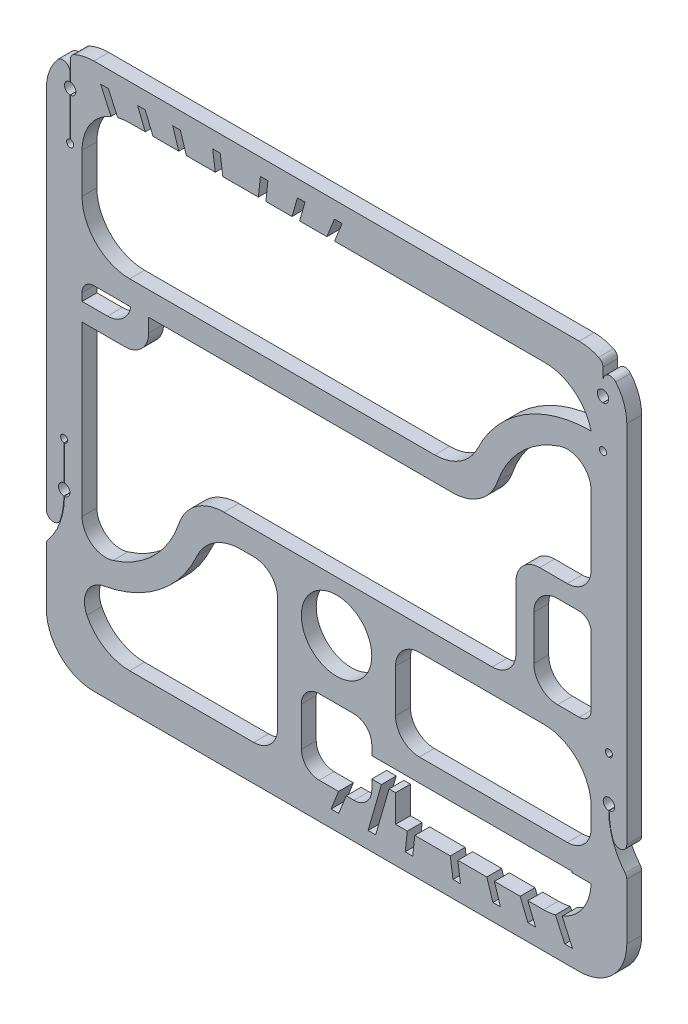
SolidWorks part; units mm, degrees
ref_plane "Front Plane" through (0, 0, 0) normal (0, 0, 1) x (1, 0, 0)
ref_plane "Top Plane" through (0, 0, 0) normal (0, 1, 0) x (1, 0, 0)
ref_plane "Right Plane" through (0, 0, 0) normal (1, 0, 0) x (0, 0, -1)
sketch "Sketch1" plane through (0, 0, 0) normal (0, 0, 1) x (1, 0, 0)
  line L0 (44.642, 21.8842) -> (44.642, 18.0742) construction
  line L1 (-10.1934, 21.8842) -> (51.7832, 21.8842)
  line L2 (-10.1934, 21.8842) -> (-10.1934, -36.406)
  line L3 (-10.1934, -36.406) -> (51.7832, -36.406)
  line L4 (51.7832, 21.8842) -> (51.7832, -36.406)
  line L5 (47.9732, -32.596) -> (-6.3834, -32.596)
  line L6 (47.9732, -32.596) -> (47.9732, 18.0742)
  line L7 (47.9732, 18.0742) -> (-6.3834, 18.0742)
  line L8 (-6.3834, -32.596) -> (-6.3834, 18.0742)
  line L9 (44.642, 19.9792) -> (-35.1587, 19.9792) construction
  line L10 (-6.3834, -31.0517) -> (-10.1934, -31.0517) construction
  line L11 (-8.2884, -31.0517) -> (-8.2884, 6.9585) construction
  line L12 (20.6521, 19.9792) -> (21.1982, 19.9792) construction
  line L14 (3.0779, -32.596) -> (3.0779, -36.406) construction
  line L15 (3.0779, -34.501) -> (37.3423, -34.501) construction
  line L16 (47.9732, -11.3911) -> (47.9732, 12.9942) construction
  line L17 (51.7832, 15.2205) -> (47.9732, 15.2205) construction
  line L18 (49.8782, 15.2205) -> (49.8782, -0.9437) construction
  line L20 (20.9378, -34.501) -> (20.3916, -34.501) construction
  line L21 (-6.3834, 8.0412) -> (-6.3834, -11.3911) construction
  dimension "D1" = 3.81
  dimension "D2" = 3.81
extrude "Boss-Extrude1" add sketch "Sketch1" along normal blind 1.5875
sketch "Sketch2" plane through (0, 0, 0) normal (0, 0, -1) x (-1, 0, 0)
  line L0 (-47.9732, -32.596) -> (-47.9732, 18.0742) construction
  line L1 (-34.8696, 3.653) -> (6.3834, 3.653)
  line L2 (-47.9732, 3.653) -> (-47.9732, 0.8076)
  line L3 (-37.4096, 1.113) -> (6.3834, 1.113)
  line L4 (6.3834, 3.653) -> (6.3834, 1.113)
  line L5 (6.3834, 18.0742) -> (6.3834, -32.596) construction
  line L6 (-33.4496, 1.113) -> (-36.4496, 1.113) construction
  line L7 (1.2504, -12.887) -> (-36.4496, -12.887) construction
  line L8 (-47.9732, -15.427) -> (-6.8239, -15.427)
  line L9 (-47.9732, -15.427) -> (-47.9732, -12.887)
  line L10 (-47.9732, -12.887) -> (-4.5259, -12.887)
  line L11 (1.357, -21.2563) -> (14.2432, -21.2563) construction
  line L12 (6.3834, -23.7963) -> (6.3834, -26.3363)
  line L13 (-47.9732, 14.2166) -> (-47.9732, 11.6766)
  arc A0 (-47.9732, 11.6766) -> (-37.4096, 1.113) centre (-47.9732, 1.113) cw
  arc A1 (-47.9732, 14.2166) -> (-34.8696, 3.653) centre (-47.9732, 0.8076) cw
  arc A2 (6.3834, -23.7963) -> (-4.5259, -12.887) centre (6.3834, -12.887) cw
  arc A3 (-6.8239, -15.427) -> (6.3834, -26.3363) centre (6.3834, -12.887) ccw
  circle A5 centre (1.357, -18.2591) radius 2.9972 construction
  line M5 (-47.9732, -32.596) -> (-47.9732, 18.0742)
  line M7 (6.3834, 18.0742) -> (6.3834, -32.596)
  dimension "D5" = 2.54
  dimension "D1" = 2.54
  dimension "D2" = 2.54
  dimension "D3" = 2.54
  dimension "D4" = 2.54
  dimension "D6" = 2.54
  dimension "D7" = 2.54
extrude "Boss-Extrude2" add sketch "Sketch2" against normal up to surface (1.5875 mm away) contours A1 A0 L3 L1 M5 M7 | L10 L8 M5 M7 region at (14.2431, 3.0939, 0) region at (-5.8234, -25.0663, 0) up to face at (20.7949, -7.2609, 1.5875)
sketch "Sketch3" plane through (0, 0, 0) normal (0, 0, -1) x (-1, 0, 0)
  line L0 (-47.9732, -1.1649) -> (-39.9496, -1.1649)
  line L1 (-47.9732, -12.887) -> (-47.9732, 11.6766) construction
  line L2 (-39.9496, -4.387) -> (-39.9496, -11.387) construction
  line L3 (-39.9496, -1.1649) -> (-39.9496, -12.887)
  line L4 (-47.9732, -12.887) -> (-4.5259, -12.887) construction
  line L5 (-39.9496, -12.887) -> (-41.8546, -12.887)
  line L6 (-41.8546, -12.887) -> (-41.8546, -3.0699)
  line L7 (-41.8546, -3.0699) -> (-47.9732, -3.0699)
  line L8 (-47.9732, -3.0699) -> (-47.9732, -1.1649)
  line L9 (-42.9468, 0.7401) -> (-53.4831, 0.7401) construction
  line L10 (-0.7296, 1.113) -> (-0.7296, -2.887)
  line L11 (-37.4096, 1.113) -> (6.3834, 1.113) construction
  line L12 (-1.9996, -2.887) -> (1.2504, -2.887) construction
  line L13 (-0.7296, -2.887) -> (6.3834, -2.887)
  line L14 (6.3834, 1.113) -> (6.3834, -23.7963) construction
  line L15 (6.3834, -2.887) -> (6.3834, -0.982)
  line L16 (6.3834, -0.982) -> (1.1754, -0.982)
  line L17 (1.1754, -0.982) -> (1.1754, 1.113)
  line L18 (1.1754, 1.113) -> (-0.7296, 1.113)
  circle A0 centre (-42.9468, 3.7373) radius 2.9972 construction
  dimension "D1" = 1.905
  dimension "D2" = 1.905
  dimension "D3" = 1.905
  dimension "D4" = 1.905
  dimension "D5" = 1.27
  dimension "D6" = 1.905
extrude "Boss-Extrude3" add sketch "Sketch3" against normal up to surface (1.5875 mm away) up to face at (20.8645, -5.9566, 1.5875)
fillet "Fillet1" radius 5.08 4 edges at (51.7832, -36.406, 0.7937) (-10.1934, -36.406, 0.7937) (-10.1934, 21.8842, 0.7937) (51.7832, 21.8842, 0.7937)
fillet "Fillet2" radius 5.08 10 edges at (6.8239, -15.427, 0.7937) (47.9732, -15.427, 0.7937) (47.9732, -32.596, 0.7937) (-6.3834, -32.596, 0.7937) (34.8696, 3.653, 0.7938) (-6.3834, 3.653, 0.7937) (47.9732, 18.0742, 0.7937) (-6.3834, 18.0742, 0.7937) (4.5259, -12.887, 0.7937) (37.4096, 1.113, 0.7938)
fillet "Fillet3" radius 2.54 10 edges at (41.8546, -3.0699, 0.7938) (39.9496, -12.887, 0.7938) (41.8546, -12.887, 0.7938) (39.9496, -1.1649, 0.7938) (47.9732, -1.1649, 0.7938) (-1.1754, -0.982, 0.7938) (0.7296, -2.887, 0.7938) (47.9732, 11.6766, 0.7937) (-6.3834, -26.3363, 0.7937) (-6.3834, -23.7963, 0.7937)
fillet "Fillet4" radius 1.27 3 edges at (47.9732, -12.887, 0.7937) (47.9732, -3.0699, 0.7938) (-6.3834, 1.113, 0.7938)
sketch "Sketch5" plane through (0, 0, 0) normal (0, 0, -1) x (-1, 0, 0)
  line L0 (-42.8932, -15.427) -> (-10.5066, -15.427) construction
  line L1 (-27.0941, -15.427) -> (-14.4957, -15.427)
  line L2 (-27.0941, -15.427) -> (-27.0941, -32.596)
  line L3 (-27.0941, -32.596) -> (-14.4957, -32.596)
  line L4 (-14.4957, -15.427) -> (-14.4957, -32.596)
  line L5 (1.3034, -32.596) -> (-42.8932, -32.596) construction
  line L6 (-24.5541, -18.2972) -> (-27.0941, -18.2972) construction
  line L9 (-17.0357, -18.2972) -> (-14.4957, -18.2972) construction
  circle A1 centre (-20.7949, -18.2972) radius 3.7592 construction
  dimension "D1" = 2.54
extrude "Boss-Extrude4" add sketch "Sketch5" against normal up to surface (1.5875 mm away) up to face at (-4.5227, -0.0173, 1.5875)
sketch "Sketch6" plane through (0, 0, 0) normal (0, 0, -1) x (-1, 0, 0)
  circle A0 centre (-20.7949, -18.2972) radius 3.7592 construction
  circle A1 centre (-20.7949, -18.2972) radius 3.7592
extrude "Cut-Extrude2" cut sketch "Sketch6" against normal up to surface (1.5875 mm away) up to face at (4.768, -24.4396, 1.5875)
sketch "Sketch7" plane through (0, 0, 0) normal (0, 0, -1) x (-1, 0, 0)
  line L0 (-27.0941, -15.427) -> (-27.0941, -32.596) construction
  line L1 (-24.5541, -24.5964) -> (-17.0357, -24.5964)
  line L2 (-24.5541, -24.5964) -> (-24.5541, -32.596)
  line L3 (-24.5541, -32.596) -> (-17.0357, -32.596)
  line L4 (-17.0357, -24.5964) -> (-17.0357, -32.596)
  line L5 (-14.4957, -32.596) -> (-14.4957, -15.427) construction
  line L6 (1.3034, -32.596) -> (-14.4957, -32.596) construction
  line L7 (-20.7949, -22.0564) -> (-6.5424, -22.0564) construction
  line L8 (-20.7949, -22.0564) -> (-20.7949, -21.3452) construction
  circle A0 centre (-20.7949, -18.2972) radius 3.7592 construction
  dimension "D1" = 2.54
  dimension "D2" = 2.54
  dimension "D3" = 2.54
extrude "Cut-Extrude3" cut sketch "Sketch7" against normal up to surface (1.5875 mm away) up to face at (24.5541, -18.2972, 1.5875)
fillet "Fillet5" radius 1.905 4 edges at (24.5541, -32.596, 0.7937) (17.0357, -32.596, 0.7938) (17.0357, -24.5964, 0.7938) (24.5541, -24.5964, 0.7938)
sketch "Sketch8" plane through (0, 0, 0) normal (0, 0, -1) x (-1, 0, 0)
  line L0 (-47.9732, -27.516) -> (-47.9732, -20.507) construction
  line L1 (-47.9732, -25.103) -> (-27.0941, -25.103)
  line L2 (-47.9732, -25.103) -> (-47.9732, -27.643)
  line L3 (-47.9732, -27.643) -> (-27.0941, -27.643)
  line L4 (-27.0941, -25.103) -> (-27.0941, -27.643)
  line L5 (-27.0941, -15.427) -> (-27.0941, -32.596) construction
  line L6 (-45.7916, -27.643) -> (-20.3916, -27.643) construction
  dimension "D1" = 2.54
extrude "Boss-Extrude5" add sketch "Sketch8" against normal up to surface (1.5875 mm away) up to face at (20.7949, -28.5962, 1.5875)
fillet "Fillet6" radius 2.54 5 edges at (27.0941, -15.427, 0.7937) (14.4957, -15.427, 0.7937) (14.4957, -32.596, 0.7937) (27.0941, -25.103, 0.7937) (47.9732, -25.103, 0.7937)
sketch "Sketch4" plane through (0, 0, 0) normal (0, 0, -1) x (-1, 0, 0)
  line L0 (3.2504, -2.887) -> (4.7504, -4.387) construction
  line L1 (4.7504, -11.387) -> (3.2504, -12.887) construction
  line L2 (3.2504, -2.887) -> (4.7504, -4.387)
  line L3 (4.7504, -11.387) -> (3.2504, -12.887)
  line L4 (4.7504, -4.387) -> (4.7504, -11.387) construction
  line L5 (4.7504, -4.387) -> (4.7504, -11.387)
  line L6 (3.2504, -2.887) -> (3.2504, -12.887)
  line L32 (4.2018, 13.1212) -> (4.2018, 15.0262)
  line L33 (4.2018, 15.0262) -> (1.9539, 15.0262)
  line L34 (1.9539, 15.0262) -> (4.2018, 19.9792)
  line L35 (4.2018, 19.9792) -> (3.6556, 19.9792)
  line L36 (3.6556, 19.9792) -> (1.4078, 15.0262)
  line L37 (1.4078, 15.0262) -> (-1.7417, 15.0262)
  line L38 (-1.7417, 15.0262) -> (0.2648, 19.9792)
  line L39 (0.2648, 19.9792) -> (-0.2814, 19.9792)
  line L40 (-0.2814, 19.9792) -> (-2.2879, 15.0262)
  line L41 (-2.2879, 15.0262) -> (-5.0437, 15.0262)
  line L42 (-5.0437, 15.0262) -> (-3.469, 19.9792)
  line L43 (-3.469, 19.9792) -> (-4.0152, 19.9792)
  line L44 (-4.0152, 19.9792) -> (-5.5899, 15.0262)
  line L45 (-5.5899, 15.0262) -> (-8.3965, 15.0262)
  line L46 (-8.3965, 15.0262) -> (-7.7108, 19.9792)
  line L47 (-7.7108, 19.9792) -> (-8.257, 19.9792)
  line L48 (-8.257, 19.9792) -> (-8.9427, 15.0262)
  line L49 (-8.9427, 15.0262) -> (-12.2319, 15.0262)
  line L50 (-12.2319, 15.0262) -> (-12.7781, 19.9792)
  line L51 (-12.7781, 19.9792) -> (-13.3242, 19.9792)
  line L52 (-13.3242, 19.9792) -> (-12.7781, 15.0262)
  line L53 (-12.7781, 15.0262) -> (-15.2926, 15.0262)
  line L54 (-15.2926, 15.0262) -> (-16.7151, 19.9792)
  line L55 (-16.7151, 19.9792) -> (-17.2612, 19.9792)
  line L56 (-17.2612, 19.9792) -> (-15.8388, 15.0262)
  line L57 (-15.8388, 15.0262) -> (-18.6963, 15.0262)
  line L58 (-18.6963, 15.0262) -> (-20.6521, 19.9792)
  line L59 (-20.6521, 19.9792) -> (-21.1982, 19.9792)
  line L60 (-21.1982, 19.9792) -> (-19.2425, 15.0262)
  line L61 (-19.2425, 15.0262) -> (-21.1982, 15.0262)
  line L62 (-21.1982, 15.0262) -> (-21.1982, 13.1212)
  line L63 (-21.1982, 13.1212) -> (4.2018, 13.1212)
  line L64 (4.2018, 13.1212) -> (4.2018, 15.0262) construction
  line L65 (4.2018, 15.0262) -> (1.9539, 15.0262) construction
  line L66 (1.9539, 15.0262) -> (4.2018, 19.9792) construction
  line L67 (4.2018, 19.9792) -> (3.6556, 19.9792) construction
  line L68 (3.6556, 19.9792) -> (1.4078, 15.0262) construction
  line L69 (1.4078, 15.0262) -> (-1.7417, 15.0262) construction
  line L70 (-1.7417, 15.0262) -> (0.2648, 19.9792) construction
  line L71 (0.2648, 19.9792) -> (-0.2814, 19.9792) construction
  line L72 (-0.2814, 19.9792) -> (-2.2879, 15.0262) construction
  line L73 (-2.2879, 15.0262) -> (-5.0437, 15.0262) construction
  line L74 (-5.0437, 15.0262) -> (-3.469, 19.9792) construction
  line L75 (-3.469, 19.9792) -> (-4.0152, 19.9792) construction
  line L76 (-4.0152, 19.9792) -> (-5.5899, 15.0262) construction
  line L77 (-5.5899, 15.0262) -> (-8.3965, 15.0262) construction
  line L78 (-8.3965, 15.0262) -> (-7.7108, 19.9792) construction
  line L79 (-7.7108, 19.9792) -> (-8.257, 19.9792) construction
  line L80 (-8.257, 19.9792) -> (-8.9427, 15.0262) construction
  line L81 (-8.9427, 15.0262) -> (-12.2319, 15.0262) construction
  line L82 (-12.2319, 15.0262) -> (-12.7781, 19.9792) construction
  line L83 (-12.7781, 19.9792) -> (-13.3242, 19.9792) construction
  line L84 (-13.3242, 19.9792) -> (-12.7781, 15.0262) construction
  line L85 (-12.7781, 15.0262) -> (-15.2926, 15.0262) construction
  line L86 (-15.2926, 15.0262) -> (-16.7151, 19.9792) construction
  line L87 (-16.7151, 19.9792) -> (-17.2612, 19.9792) construction
  line L88 (-17.2612, 19.9792) -> (-15.8388, 15.0262) construction
  line L89 (-15.8388, 15.0262) -> (-18.6963, 15.0262) construction
  line L90 (-18.6963, 15.0262) -> (-20.6521, 19.9792) construction
  line L91 (-20.6521, 19.9792) -> (-21.1982, 19.9792) construction
  line L92 (-21.1982, 19.9792) -> (-19.2425, 15.0262) construction
  line L93 (-19.2425, 15.0262) -> (-21.1982, 15.0262) construction
  line L94 (-21.1982, 15.0262) -> (-21.1982, 13.1212) construction
  line L95 (-21.1982, 13.1212) -> (4.2018, 13.1212) construction
  line L96 (-45.7916, -27.643) -> (-45.7916, -29.548)
  line L97 (-45.7916, -29.548) -> (-43.5438, -29.548)
  line L98 (-43.5438, -29.548) -> (-45.7916, -34.501)
  line L99 (-45.7916, -34.501) -> (-45.2455, -34.501)
  line L100 (-45.2455, -34.501) -> (-42.9976, -29.548)
  line L101 (-42.9976, -29.548) -> (-39.8482, -29.548)
  line L102 (-39.8482, -29.548) -> (-41.8546, -34.501)
  line L103 (-41.8546, -34.501) -> (-41.3085, -34.501)
  line L104 (-41.3085, -34.501) -> (-39.302, -29.548)
  line L105 (-39.302, -29.548) -> (-36.5462, -29.548)
  line L106 (-36.5462, -29.548) -> (-38.1208, -34.501)
  line L107 (-38.1208, -34.501) -> (-37.5747, -34.501)
  line L108 (-37.5747, -34.501) -> (-36, -29.548)
  line L109 (-36, -29.548) -> (-33.1934, -29.548)
  line L110 (-33.1934, -29.548) -> (-33.879, -34.501)
  line L111 (-33.879, -34.501) -> (-33.3329, -34.501)
  line L112 (-33.3329, -34.501) -> (-32.6472, -29.548)
  line L113 (-32.6472, -29.548) -> (-29.358, -29.548)
  line L114 (-29.358, -29.548) -> (-28.8118, -34.501)
  line L115 (-28.8118, -34.501) -> (-28.2656, -34.501)
  line L116 (-28.2656, -34.501) -> (-28.8118, -29.548)
  line L117 (-28.8118, -29.548) -> (-26.2973, -29.548)
  line L118 (-26.2973, -29.548) -> (-24.8748, -34.501)
  line L119 (-24.8748, -34.501) -> (-24.3286, -34.501)
  line L120 (-24.3286, -34.501) -> (-25.7511, -29.548)
  line L121 (-25.7511, -29.548) -> (-22.8935, -29.548)
  line L122 (-22.8935, -29.548) -> (-20.9378, -34.501)
  line L123 (-20.9378, -34.501) -> (-20.3916, -34.501)
  line L124 (-20.3916, -34.501) -> (-22.3474, -29.548)
  line L125 (-22.3474, -29.548) -> (-20.3916, -29.548)
  line L126 (-20.3916, -29.548) -> (-20.3916, -27.643)
  line L127 (-20.3916, -27.643) -> (-45.7916, -27.643)
  line L128 (-45.7916, -27.643) -> (-45.7916, -29.548) construction
  line L129 (-45.7916, -29.548) -> (-43.5438, -29.548) construction
  line L130 (-43.5438, -29.548) -> (-45.7916, -34.501) construction
  line L131 (-45.7916, -34.501) -> (-45.2455, -34.501) construction
  line L132 (-45.2455, -34.501) -> (-42.9976, -29.548) construction
  line L133 (-42.9976, -29.548) -> (-39.8482, -29.548) construction
  line L134 (-39.8482, -29.548) -> (-41.8546, -34.501) construction
  line L135 (-41.8546, -34.501) -> (-41.3085, -34.501) construction
  line L136 (-41.3085, -34.501) -> (-39.302, -29.548) construction
  line L137 (-39.302, -29.548) -> (-36.5462, -29.548) construction
  line L138 (-36.5462, -29.548) -> (-38.1208, -34.501) construction
  line L139 (-38.1208, -34.501) -> (-37.5747, -34.501) construction
  line L140 (-37.5747, -34.501) -> (-36, -29.548) construction
  line L141 (-36, -29.548) -> (-33.1934, -29.548) construction
  line L142 (-33.1934, -29.548) -> (-33.879, -34.501) construction
  line L143 (-33.879, -34.501) -> (-33.3329, -34.501) construction
  line L144 (-33.3329, -34.501) -> (-32.6472, -29.548) construction
  line L145 (-32.6472, -29.548) -> (-29.358, -29.548) construction
  line L146 (-29.358, -29.548) -> (-28.8118, -34.501) construction
  line L147 (-28.8118, -34.501) -> (-28.2656, -34.501) construction
  line L148 (-28.2656, -34.501) -> (-28.8118, -29.548) construction
  line L149 (-28.8118, -29.548) -> (-26.2973, -29.548) construction
  line L150 (-26.2973, -29.548) -> (-24.8748, -34.501) construction
  line L151 (-24.8748, -34.501) -> (-24.3286, -34.501) construction
  line L152 (-24.3286, -34.501) -> (-25.7511, -29.548) construction
  line L153 (-25.7511, -29.548) -> (-22.8935, -29.548) construction
  line L154 (-22.8935, -29.548) -> (-20.9378, -34.501) construction
  line L155 (-20.9378, -34.501) -> (-20.3916, -34.501) construction
  line L156 (-20.3916, -34.501) -> (-22.3474, -29.548) construction
  line L157 (-22.3474, -29.548) -> (-20.3916, -29.548) construction
  line L158 (-20.3916, -29.548) -> (-20.3916, -27.643) construction
  line L159 (-20.3916, -27.643) -> (-45.7916, -27.643) construction
  line L263 (4.3288, 12.9942) -> (4.3288, 15.1532)
  line L264 (4.3288, 15.1532) -> (2.151, 15.1532)
  line L265 (2.151, 15.1532) -> (4.3989, 20.1062)
  line L266 (4.3989, 20.1062) -> (3.5738, 20.1062)
  line L267 (3.5738, 20.1062) -> (1.3259, 15.1532)
  line L268 (1.3259, 15.1532) -> (-1.5532, 15.1532)
  line L269 (-1.5532, 15.1532) -> (0.4532, 20.1062)
  line L270 (0.4532, 20.1062) -> (-0.367, 20.1062)
  line L271 (-0.367, 20.1062) -> (-2.3735, 15.1532)
  line L272 (-2.3735, 15.1532) -> (-4.8701, 15.1532)
  line L273 (-4.8701, 15.1532) -> (-3.2954, 20.1062)
  line L274 (-3.2954, 20.1062) -> (-4.1081, 20.1062)
  line L275 (-4.1081, 20.1062) -> (-5.6828, 15.1532)
  line L276 (-5.6828, 15.1532) -> (-8.2507, 15.1532)
  line L277 (-8.2507, 15.1532) -> (-7.565, 20.1062)
  line L278 (-7.565, 20.1062) -> (-8.3676, 20.1062)
  line L279 (-8.3676, 20.1062) -> (-9.0533, 15.1532)
  line L280 (-9.0533, 15.1532) -> (-12.1181, 15.1532)
  line L281 (-12.1181, 15.1532) -> (-12.6643, 20.1062)
  line L282 (-12.6643, 20.1062) -> (-13.466, 20.1062)
  line L283 (-13.466, 20.1062) -> (-12.9198, 15.1532)
  line L284 (-12.9198, 15.1532) -> (-15.1969, 15.1532)
  line L285 (-15.1969, 15.1532) -> (-16.6194, 20.1062)
  line L286 (-16.6194, 20.1062) -> (-17.4298, 20.1062)
  line L287 (-17.4298, 20.1062) -> (-16.0074, 15.1532)
  line L288 (-16.0074, 15.1532) -> (-18.6099, 15.1532)
  line L289 (-18.6099, 15.1532) -> (-20.5657, 20.1062)
  line L290 (-20.5657, 20.1062) -> (-21.3849, 20.1062)
  line L291 (-21.3849, 20.1062) -> (-19.4292, 15.1532)
  line L292 (-19.4292, 15.1532) -> (-21.3252, 15.1532)
  line L293 (-21.3252, 15.1532) -> (-21.3252, 12.9942)
  line L294 (-21.3252, 12.9942) -> (4.3288, 12.9942)
  line L295 (-45.9186, -27.516) -> (-45.9186, -29.675)
  line L296 (-45.9186, -29.675) -> (-43.7409, -29.675)
  line L297 (-43.7409, -29.675) -> (-45.9887, -34.628)
  line L298 (-45.9887, -34.628) -> (-45.1636, -34.628)
  line L299 (-45.1636, -34.628) -> (-42.9158, -29.675)
  line L300 (-42.9158, -29.675) -> (-40.0367, -29.675)
  line L301 (-40.0367, -29.675) -> (-42.0431, -34.628)
  line L302 (-42.0431, -34.628) -> (-41.2229, -34.628)
  line L303 (-41.2229, -34.628) -> (-39.2164, -29.675)
  line L304 (-39.2164, -29.675) -> (-36.7198, -29.675)
  line L305 (-36.7198, -29.675) -> (-38.2945, -34.628)
  line L306 (-38.2945, -34.628) -> (-37.4818, -34.628)
  line L307 (-37.4818, -34.628) -> (-35.9071, -29.675)
  line L308 (-35.9071, -29.675) -> (-33.3392, -29.675)
  line L309 (-33.3392, -29.675) -> (-34.0248, -34.628)
  line L310 (-34.0248, -34.628) -> (-33.2222, -34.628)
  line L311 (-33.2222, -34.628) -> (-32.5366, -29.675)
  line L312 (-32.5366, -29.675) -> (-29.4717, -29.675)
  line L313 (-29.4717, -29.675) -> (-28.9256, -34.628)
  line L314 (-28.9256, -34.628) -> (-28.1239, -34.628)
  line L315 (-28.1239, -34.628) -> (-28.67, -29.675)
  line L316 (-28.67, -29.675) -> (-26.3929, -29.675)
  line L317 (-26.3929, -29.675) -> (-24.9705, -34.628)
  line L318 (-24.9705, -34.628) -> (-24.16, -34.628)
  line L319 (-24.16, -34.628) -> (-25.5825, -29.675)
  line L320 (-25.5825, -29.675) -> (-22.9799, -29.675)
  line L321 (-22.9799, -29.675) -> (-21.0242, -34.628)
  line L322 (-21.0242, -34.628) -> (-20.205, -34.628)
  line L323 (-20.205, -34.628) -> (-22.1607, -29.675)
  line L324 (-22.1607, -29.675) -> (-20.2646, -29.675)
  line L325 (-20.2646, -29.675) -> (-20.2646, -27.516)
  line L326 (-20.2646, -27.516) -> (-45.9186, -27.516)
  dimension "D1" = 0
  dimension "D2" = 0
  dimension "D3" = 0.127
  dimension "D4" = 0.127
extrude "Cut-Extrude1" cut sketch "Sketch4" against normal up to surface (1.5875 mm away) up to face at (37.2819, -20.5167, 1.5875)
sketch "Sketch9" plane through (0, 0, 0) normal (0, 0, -1) x (-1, 0, 0)
  circle A0 centre (-49.2432, 18.0742) radius 0.6096 construction
  circle A1 centre (7.6534, 18.0742) radius 0.6096 construction
  circle A2 centre (8.2884, -19.3286) radius 0.6096 construction
  circle A3 centre (-49.8782, -19.3286) radius 0.6096 construction
  circle A4 centre (-49.2432, 18.0742) radius 0.6096
  circle A5 centre (7.6534, 18.0742) radius 0.6096
  circle A6 centre (8.2884, -19.3286) radius 0.6096
  circle A7 centre (-49.8782, -19.3286) radius 0.6096
extrude "Cut-Extrude4" cut sketch "Sketch9" against normal up to surface (1.5875 mm away) up to face at (31.4097, -31.792, 1.5875)
sketch "Sketch10" plane through (0, 0, 1.5875) normal (0, 0, 1) x (1, 0, 0)
  line L0 (-7.6407, 18.6837) -> (-7.6407, 20.7449) construction
  line L1 (-7.6407, 13.375) -> (-7.6407, 17.4647) construction
  line L2 (-7.6661, 17.4647) -> (-7.6661, 13.375) construction
  line L3 (-7.6661, 19.5715) -> (-7.6661, 18.6837) construction
  line L4 (-7.6407, 18.6837) -> (-7.6407, 20.7449)
  line L5 (-7.6407, 13.375) -> (-7.6407, 17.4647)
  line L6 (-7.6661, 17.4647) -> (-7.6661, 13.375)
  line L7 (-7.6661, 19.5715) -> (-7.6661, 18.6837)
  line L8 (49.2305, 18.6837) -> (49.2305, 20.7449) construction
  line L9 (49.2305, 13.375) -> (49.2305, 17.4647) construction
  line L10 (49.2559, 17.4647) -> (49.2559, 13.375) construction
  line L11 (49.2559, 19.5715) -> (49.2559, 18.6837) construction
  line L12 (49.2305, 18.6837) -> (49.2305, 20.7449)
  line L13 (49.2305, 13.375) -> (49.2305, 17.4647)
  line L14 (49.2559, 17.4647) -> (49.2559, 13.375)
  line L15 (49.2559, 19.5715) -> (49.2559, 18.6837)
  line L16 (49.8909, -15.0101) -> (49.8909, -18.7191) construction
  line L17 (49.8655, -15.0101) -> (49.8655, -18.7191) construction
  line L18 (49.8909, -15.0101) -> (49.8909, -18.7191)
  line L19 (49.8655, -15.0101) -> (49.8655, -18.7191)
  line L20 (-8.2757, -15.0101) -> (-8.2757, -18.7191) construction
  line L21 (-8.3011, -15.0101) -> (-8.3011, -18.7191) construction
  line L22 (-8.2757, -15.0101) -> (-8.2757, -18.7191)
  line L23 (-8.3011, -15.0101) -> (-8.3011, -18.7191)
  line L24 (51.7832, -31.326) -> (51.7832, 16.8042) construction
  line L25 (51.7832, -25.3365) -> (51.7832, -22.131)
  line L26 (-10.1934, 16.8042) -> (-10.1934, -31.326) construction
  line L27 (-10.1934, -22.131) -> (-10.1934, -25.3365)
  arc A1 (-7.1902, 21.4403) -> (-7.6407, 20.7449) centre (-6.8787, 20.7449) ccw construction
  arc A2 (-7.6661, 13.375) -> (-7.6407, 13.375) centre (-7.6534, 12.9942) ccw construction
  arc A3 (-7.6661, 19.5715) -> (-9.013, 20.0598) centre (-8.4281, 19.5715) ccw construction
  arc A4 (-5.1134, 21.8842) -> (-10.1934, 16.8042) centre (-5.1134, 16.8042) ccw construction
  arc A5 (-7.1902, 21.4403) -> (-7.6407, 20.7449) centre (-6.8787, 20.7449) ccw
  arc A6 (-7.6661, 13.375) -> (-7.6407, 13.375) centre (-7.6534, 12.9942) ccw
  arc A7 (-7.6661, 19.5715) -> (-9.013, 20.0598) centre (-8.4281, 19.5715) ccw
  arc A8 (-7.1902, 21.4403) -> (-9.013, 20.0598) centre (-5.1134, 16.8042) ccw
  circle A9 centre (-7.6534, 18.0742) radius 0.6096 construction
  arc A10 (-7.6407, 18.6837) -> (-7.6661, 18.6837) centre (-7.6534, 18.0742) ccw
  arc A11 (-7.6661, 17.4647) -> (-7.6407, 17.4647) centre (-7.6534, 18.0742) ccw
  arc A12 (49.2305, 20.7449) -> (48.7801, 21.4403) centre (48.4685, 20.7449) ccw construction
  arc A13 (49.2305, 13.375) -> (49.2559, 13.375) centre (49.2432, 12.9942) ccw construction
  arc A14 (50.6029, 20.0598) -> (49.2559, 19.5715) centre (50.0179, 19.5715) ccw construction
  arc A15 (49.2305, 20.7449) -> (48.7801, 21.4403) centre (48.4685, 20.7449) ccw
  arc A16 (49.2305, 13.375) -> (49.2559, 13.375) centre (49.2432, 12.9942) ccw
  arc A17 (50.6029, 20.0598) -> (49.2559, 19.5715) centre (50.0179, 19.5715) ccw
  arc A18 (49.8909, -15.0101) -> (49.8655, -15.0101) centre (49.8782, -14.6293) ccw construction
  arc A19 (49.9036, -19.9377) -> (50.2983, -22.3718) centre (57.6041, -19.9382) ccw construction
  arc A20 (49.8528, -19.9377) -> (51.6105, -24.8533) centre (57.6041, -19.9382) ccw construction
  arc A21 (50.2983, -22.3718) -> (51.7832, -22.131) centre (51.0212, -22.131) ccw construction
  arc A22 (51.7832, -25.3365) -> (51.6105, -24.8533) centre (51.0212, -25.3365) ccw construction
  arc A23 (49.8909, -15.0101) -> (49.8655, -15.0101) centre (49.8782, -14.6293) ccw
  arc A24 (49.9036, -19.9377) -> (50.2983, -22.3718) centre (57.6041, -19.9382) ccw
  arc A25 (49.8528, -19.9377) -> (51.6105, -24.8533) centre (57.6041, -19.9382) ccw
  arc A26 (50.2983, -22.3718) -> (51.7832, -22.131) centre (51.0212, -22.131) ccw
  arc A27 (51.7832, -25.3365) -> (51.6105, -24.8533) centre (51.0212, -25.3365) ccw
  arc A28 (-10.1934, -22.131) -> (-8.7084, -22.3718) centre (-9.4314, -22.131) ccw construction
  arc A29 (-10.0206, -24.8533) -> (-8.263, -19.9377) centre (-16.0142, -19.9382) ccw construction
  arc A30 (-8.7084, -22.3718) -> (-8.3138, -19.9377) centre (-16.0142, -19.9382) ccw construction
  arc A31 (-8.2757, -15.0101) -> (-8.3011, -15.0101) centre (-8.2884, -14.6293) ccw construction
  arc A32 (-10.1934, -22.131) -> (-8.7084, -22.3718) centre (-9.4314, -22.131) ccw
  arc A33 (-10.0206, -24.8533) -> (-8.263, -19.9377) centre (-16.0142, -19.9382) ccw
  arc A34 (-8.7084, -22.3718) -> (-8.3138, -19.9377) centre (-16.0142, -19.9382) ccw
  arc A35 (-8.2757, -15.0101) -> (-8.3011, -15.0101) centre (-8.2884, -14.6293) ccw
  arc A36 (51.7832, 16.8042) -> (46.7032, 21.8842) centre (46.7032, 16.8042) ccw construction
  arc A37 (50.6029, 20.0598) -> (48.7801, 21.4403) centre (46.7032, 16.8042) ccw
  circle A38 centre (49.2432, 18.0742) radius 0.6096 construction
  arc A39 (49.2559, 18.6837) -> (49.2305, 18.6837) centre (49.2432, 18.0742) ccw
  arc A40 (49.2305, 17.4647) -> (49.2559, 17.4647) centre (49.2432, 18.0742) ccw
  circle A41 centre (49.8782, -19.3286) radius 0.6096 construction
  arc A42 (49.8909, -18.7191) -> (49.8655, -18.7191) centre (49.8782, -19.3286) ccw
  arc A43 (49.8528, -19.9377) -> (49.9036, -19.9377) centre (49.8782, -19.3286) ccw
  circle A44 centre (-8.2884, -19.3286) radius 0.6096 construction
  arc A45 (-8.2757, -18.7191) -> (-8.3011, -18.7191) centre (-8.2884, -19.3286) ccw
  arc A46 (-8.3138, -19.9377) -> (-8.263, -19.9377) centre (-8.2884, -19.3286) ccw
  arc A47 (-10.0206, -24.8533) -> (-10.1934, -25.3365) centre (-9.4314, -25.3365) ccw construction
  arc A48 (-10.0206, -24.8533) -> (-10.1934, -25.3365) centre (-9.4314, -25.3365) ccw
extrude "Slots for carbon" cut sketch "Sketch10" against normal through all
